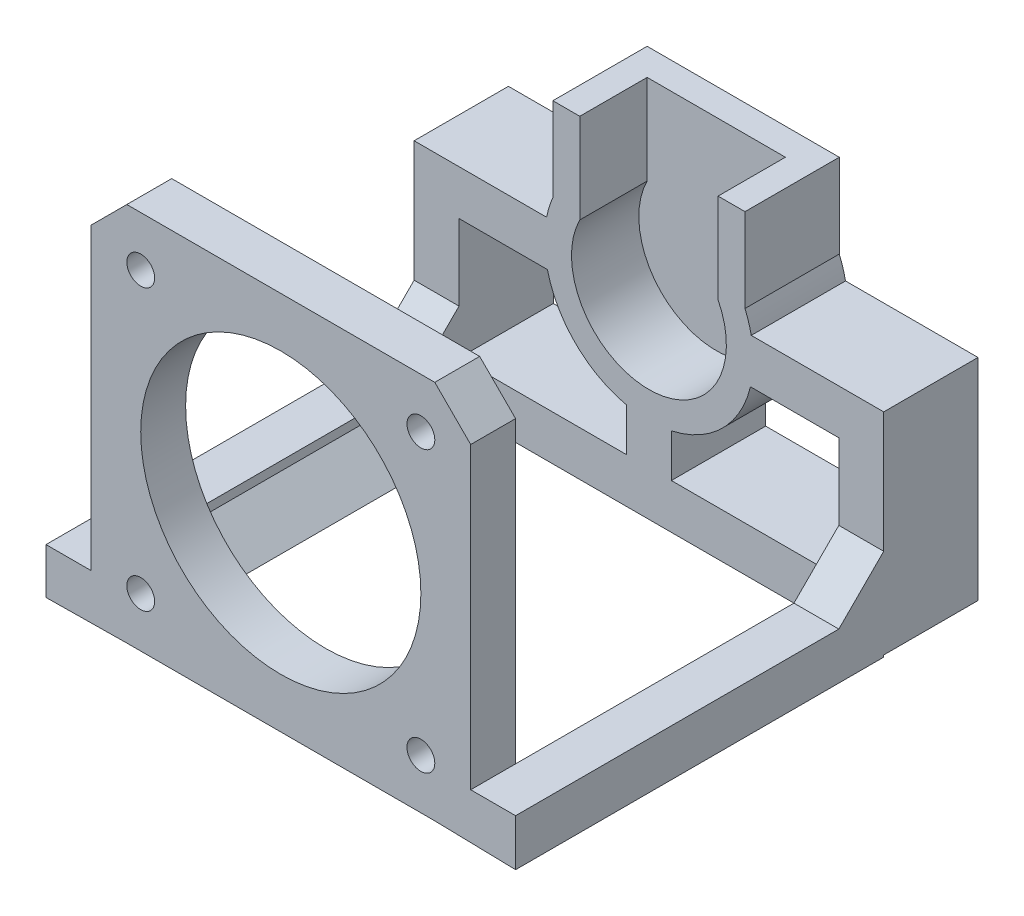
SolidWorks part; units mm, degrees
ref_plane "Front Plane" through (0, 0, 0) normal (0, 0, 1) x (1, 0, 0)
ref_plane "Top Plane" through (0, 0, 0) normal (0, 1, 0) x (1, 0, 0)
ref_plane "Right Plane" through (0, 0, 0) normal (1, 0, 0) x (0, 0, -1)
sketch "Sketch2" plane through (0, 0, 0) normal (0, 0, 1) x (1, 0, 0)
  line L0 (6.2408, -20.8452) -> (6.2408, 21.4548) construction
  line L1 (-10.9092, 21.4548) -> (23.3908, 21.4548)
  line L2 (-14.9092, 17.4548) -> (-14.9092, -16.8452)
  line L4 (27.3908, 17.4548) -> (27.3908, -16.8452)
  line L7 (-14.9092, 0.3048) -> (27.3908, 0.3048) construction
  line L8 (-14.9092, 17.4548) -> (-10.9092, 21.4548)
  line L9 (27.3908, 17.4548) -> (23.3908, 21.4548)
  line L10 (27.3908, -16.8452) -> (23.3908, -20.8452)
  line L11 (-14.9092, -16.8452) -> (-10.9092, -20.8452)
  line L12 (-10.9092, -20.8452) -> (23.3908, -20.8452)
  circle A0 centre (-9.3592, 15.9048) radius 1.55
  circle A1 centre (21.8408, 15.9048) radius 1.55
  circle A2 centre (21.8408, -15.2952) radius 1.55
  circle A3 centre (-9.3592, -15.2952) radius 1.55
  circle A4 centre (6.2408, 0.3048) radius 15.6
  point P0 (0, 0)
  point P31 (6.2408, 21.4548)
  point P33 (6.2408, -20.8452)
  point P35 (-14.9092, 0.3048)
  dimension "D3" = 15.6
  dimension "3.1" = 3.1
  dimension "D7" = 31.2
  dimension "D1" = 42.3
  dimension "D2" = 42.3
  dimension "D4" = 15.6
  dimension "D5" = 5.6569
  dimension "D6" = 135
extrude "Boss-Extrude1" add sketch "Sketch2" along normal blind 5
sketch "Sketch4" plane through (0, 0, 5) normal (0, 0, 1) x (1, 0, 0)
  line L0 (27.3908, -16.8452) -> (27.3908, 17.4548) construction
  line L1 (27.3908, 12.8048) -> (32.3908, 12.8048)
  line L2 (27.3908, 12.8048) -> (27.3908, -12.1952)
  line L4 (32.3908, 12.8048) -> (32.3908, -12.1952)
  line L5 (-12.9092, -18.8452) -> (25.3908, 19.4548) construction
  line L6 (-14.9092, -16.8452) -> (-10.9092, -20.8452) construction
  line L11 (-14.9092, 17.4548) -> (-14.9092, -16.8452) construction
  line L12 (-14.9092, 12.8048) -> (-19.9092, 12.8048)
  line L13 (-14.9092, 12.8048) -> (-14.9092, -12.1952)
  line L15 (-19.9092, 12.8048) -> (-19.9092, -12.1952)
  line L16 (27.3908, 17.4548) -> (23.3908, 21.4548) construction
  line L17 (-12.9092, 19.4548) -> (25.3908, -18.8452) construction
  line L18 (-10.9092, 21.4548) -> (-14.9092, 17.4548) construction
  line L19 (23.3908, -20.8452) -> (27.3908, -16.8452) construction
  line L20 (-14.9092, 0.3048) -> (27.3908, 0.3048)
  line L21 (32.3908, -12.1952) -> (32.3908, -21.0569)
  line L22 (23.3908, -20.8452) -> (32.3908, -21.0569)
  line L23 (-19.9092, -12.1952) -> (-19.9092, -20.951)
  line L24 (-19.9092, -20.951) -> (-10.9092, -20.8452)
  line L25 (-14.9092, -12.1952) -> (-14.9092, -16.8452)
  line L26 (-14.9092, -16.8452) -> (-10.9092, -20.8452)
  line L27 (27.3908, -12.1952) -> (27.3908, -16.8452)
  line L28 (27.3908, -16.8452) -> (23.3908, -20.8452)
  point P24 (-14.9092, 0.3048)
  point P27 (6.2408, 0.3048)
  point P29 (27.3908, 0.3048)
  line M15 (23.3908, -20.8452) -> (27.3908, -16.8452)
  line M16 (27.3908, -16.8452) -> (27.3908, 17.4548)
  line M20 (-14.9092, 17.4548) -> (-14.9092, -16.8452)
  line M21 (-14.9092, -16.8452) -> (-10.9092, -20.8452)
  dimension "D1" = 5
  dimension "5" = 5
  dimension "D2" = 25
  dimension "25" = 25
extrude "Boss-Extrude3" add sketch "Sketch4" against normal blind 41 contours L23 L24 L13 L12 L15 M21 M20 | L22 L21 L4 L1 L2 M15 M16 region at (-17.2344, -4.7669, 5) region at (29.715, -4.8104, 5)
ref_plane "Plane1" through (0, 0, -36) normal (0, 0, -1) x (-1, 0, 0)
sketch "Sketch5" plane through (0, 0, -36) normal (0, 0, -1) x (-1, 0, 0)
  line L0 (1.4592, 4.1908) -> (-13.9408, 4.1908) construction
  line L2 (-13.9408, 4.1908) -> (-13.9408, 11.1908)
  line L3 (-13.9408, 11.1908) -> (1.4592, 11.1908)
  line L4 (1.4592, 4.1908) -> (1.4592, 11.1908)
  line L5 (4.4592, 4.8491) -> (4.4592, 14.1908)
  line L6 (-16.9408, 14.1908) -> (4.4592, 14.1908)
  line L7 (-16.9408, 4.8491) -> (-16.9408, 14.1908)
  line L8 (-13.9408, 11.1908) -> (-13.9408, 14.1908)
  line L9 (1.4592, 11.1908) -> (1.4592, 14.1908)
  circle A0 centre (-6.2408, 0.3048) radius 15.6 construction
  circle A1 centre (-6.2408, 0.3048) radius 15.6 construction
  arc A2 (-13.9408, 4.1908) -> (1.4592, 4.1908) centre (-6.2408, 0.3048) ccw
  arc A3 (-16.9408, 4.8491) -> (4.4592, 4.8491) centre (-6.2408, 0.3048) ccw
  dimension "D1" = 15.4
  dimension "17.25" = 17.25
  dimension "D2" = 7
  dimension "D3" = 3
extrude "Boss-Extrude4" add sketch "Sketch5" along normal blind 7.5 separate body contours L7 A3 L5 L6 A2 L2 L3 L4 region at (6.2408, -8.6653, -36)
sketch "Sketch6" plane through (0, 0, -43.5) normal (0, 0, -1) x (-1, 0, 0)
  line L0 (-16.9408, 4.8491) -> (-16.9408, 14.1908)
  line L1 (-16.9408, 14.1908) -> (-13.9408, 14.1908) construction
  line L2 (-16.9408, 4.8491) -> (-16.9408, 14.1908) construction
  line L3 (-16.9408, 14.1908) -> (4.4592, 14.1908)
  line L4 (4.4592, 14.1908) -> (4.4592, 4.8491)
  arc A0 (-16.9408, 4.8491) -> (4.4592, 4.8491) centre (-6.2408, 0.3048) ccw
extrude "Boss-Extrude5" add sketch "Sketch6" along normal blind 3
ref_plane "Plane2" through (0, 0, -43.5) normal (0, 0, -1) x (-1, 0, 0)
sketch "Sketch8" plane through (0, 0, -43.5) normal (0, 0, -1) x (-1, 0, 0)
  line L0 (10.9092, -20.8452) -> (-23.3908, -20.8452) construction
  line L1 (-8.7408, -9.5089) -> (-3.7408, -9.5089)
  line L2 (-8.7408, -9.5089) -> (-8.7408, -20.8452)
  line L3 (-8.7408, -20.8452) -> (-3.7408, -20.8452)
  line L4 (-3.7408, -9.5089) -> (-3.7408, -20.8452)
  line L5 (-32.3908, 12.8048) -> (-32.3908, -21.0569) construction
  line L6 (19.9092, 12.8048) -> (19.9092, -20.951) construction
  line L7 (-6.2408, 14.1908) -> (-6.2408, -11.3202) construction
  line L8 (-32.3908, 2.604) -> (-17.1561, 2.604)
  line L9 (-32.3908, 2.604) -> (-32.3908, -2.396)
  line L10 (-32.3908, -2.396) -> (-17.1561, -2.396)
  line L11 (19.9092, 2.604) -> (19.9092, -2.396)
  line L12 (4.4592, 14.1908) -> (-16.9408, 14.1908) construction
  line L13 (-17.1561, 2.604) -> (-17.1561, -2.396)
  line L14 (4.1541, 2.604) -> (4.1541, -2.396)
  line L15 (4.1541, -2.396) -> (19.9092, -2.396)
  line L16 (4.1541, 2.604) -> (19.9092, 2.604)
  arc A0 (-16.9408, 4.8491) -> (4.4592, 4.8491) centre (-6.2408, 0.3048) ccw construction
  point P21 (-6.2408, -9.5089)
  dimension "D1" = 5
  dimension "D2" = 5
extrude "Boss-Extrude6" add sketch "Sketch8" along normal blind 3 and the other way up to surface other way up to face at (28.5908, -6.6275, -36)
ref_plane "Plane3" through (8.7408, -20.8452, -36) normal (-1, 0, 0) x (0, 0, 1)
sketch "Sketch12" plane through (3.7408, 0, 0) normal (-1, 0, 0) x (0, 0, 1)
  line L0 (-36, 18.6239) -> (-36, -18.6239) construction
  line L1 (-46.5, -20.8452) -> (-36, -20.8452)
  line L2 (-46.5, -20.8452) -> (-46.5, -15.8452)
  line L3 (-46.5, -15.8452) -> (-36, -15.8452)
  line L4 (-36, -20.8452) -> (-36, -15.8452)
  dimension "D1" = 5
extrude "Boss-Extrude8" add sketch "Sketch12" along normal blind 23.65
sketch "Sketch13" plane through (8.7408, 0, 0) normal (1, 0, 0) x (0, 0, -1)
  line L0 (36, -18.6239) -> (36, 18.6239) construction
  line L1 (46.5, -20.8452) -> (36, -20.8452)
  line L2 (46.5, -20.8452) -> (46.5, -15.8452)
  line L3 (46.5, -15.8452) -> (36, -15.8452)
  line L4 (36, -20.8452) -> (36, -15.8452)
  dimension "D1" = 5
extrude "Boss-Extrude9" add sketch "Sketch13" along normal blind 23.65
sketch "Sketch14" plane through (0, 0, -36) normal (0, 0, -1) x (-1, 0, 0)
  line L0 (-32.3908, -15.8452) -> (-8.7408, -15.8452) construction
  line L5 (-32.3908, 12.8048) -> (-27.3908, 12.8048)
  line L6 (-32.3908, 12.8048) -> (-32.3908, -15.8452)
  line L15 (-32.3908, -15.8452) -> (-27.3908, -15.8452)
  line L22 (-27.3908, 12.8048) -> (-27.3908, -15.8452)
  line L43 (-27.3908, -16.8452) -> (-27.3908, 12.8048) construction
  line L44 (19.9092, 12.8048) -> (19.9092, -15.8452) construction
  line L45 (14.9092, 12.8048) -> (19.9092, 12.8048)
  line L46 (14.9092, 12.8048) -> (14.9092, -15.8452)
  line L47 (14.9092, -15.8452) -> (19.9092, -15.8452)
  line L48 (19.9092, 12.8048) -> (19.9092, -15.8452)
extrude "Cut-Extrude1" cut sketch "Sketch14" against normal up to surface (41 mm away) up to face at (-10.9092, -15.2952, 5)
sketch "Sketch15" plane through (0, -15.8452, 0) normal (0, 1, 0) x (1, 0, 0)
  line L0 (18.6239, 36) -> (-18.6239, 36) construction
  line L1 (32.3908, 46.5) -> (27.3908, 46.5)
  line L2 (32.3908, 46.5) -> (32.3908, 36)
  line L3 (32.3908, 36) -> (27.3908, 36)
  line L4 (27.3908, 46.5) -> (27.3908, 36)
  line L5 (27.3908, 36) -> (27.3908, 0) construction
  line L6 (-14.9092, 36) -> (-14.9092, 0) construction
  line L7 (-19.9092, 46.5) -> (-14.9092, 46.5)
  line L8 (-19.9092, 46.5) -> (-19.9092, 36)
  line L9 (-19.9092, 36) -> (-14.9092, 36)
  line L10 (-14.9092, 46.5) -> (-14.9092, 36)
extrude "Boss-Extrude10" add sketch "Sketch15" along normal up to surface (13.4492 mm away) up to face at (-12.4877, -2.396, -41.25)
sketch "Sketch16" plane through (32.3908, 0, 0) normal (1, 0, 0) x (0, 0, -1)
  line L0 (36, -10.8452) -> (31, -15.8452)
  line L1 (36, -18.6239) -> (36, 18.6239) construction
  line L2 (36, -15.8452) -> (-5, -15.8452) construction
  line L3 (31, -15.8452) -> (36, -15.8452)
  line L4 (36, -15.8452) -> (36, -10.8452)
  dimension "D1" = 5
  dimension "D2" = 5
extrude "Boss-Extrude11" add sketch "Sketch16" against normal up to surface (5 mm away) up to face at (27.3908, -9.1206, -41.25)
sketch "Sketch18" plane through (-19.9092, 0, 0) normal (-1, 0, 0) x (0, 0, 1)
  line L0 (-36, -10.8452) -> (-31, -15.8452)
  line L1 (-36, 18.6239) -> (-36, -18.6239) construction
  line L2 (-31, -15.8452) -> (-36, -15.8452)
  line L3 (5, -15.8452) -> (-36, -15.8452) construction
  line L4 (-36, -15.8452) -> (-36, -10.8452)
  dimension "D1" = 5
  dimension "D2" = 5
extrude "Boss-Extrude12" add sketch "Sketch18" against normal up to surface (5 mm away) up to face at (-14.9092, -9.1206, -41.25)
